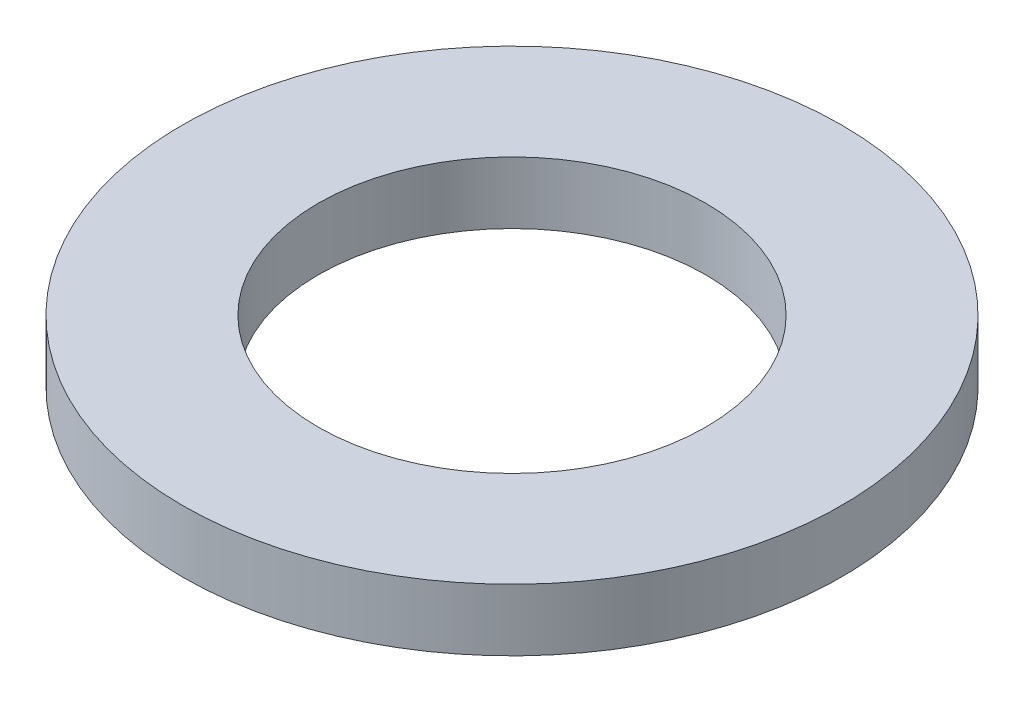
SolidWorks part; units mm, degrees
ref_plane "Front Plane" through (0, 0, 0) normal (0, 0, 1) x (1, 0, 0)
ref_plane "Top Plane" through (0, 0, 0) normal (0, 1, 0) x (1, 0, 0)
ref_plane "Right Plane" through (0, 0, 0) normal (1, 0, 0) x (0, 0, -1)
sketch "Sketch1" plane through (0, 0, 0) normal (0, 1, 0) x (1, 0, 0)
  circle A0 centre (0, 0) radius 42.5
  dimension "FLANGE_OD" = 85
extrude "Boss-Extrude1" add sketch "Sketch1" along normal blind 8
sketch "Sketch2" plane through (0, 0, 0) normal (0, 1, 0) x (1, 0, 0)
  circle A0 centre (0, 0) radius 25
  dimension "BORE_D" = 50
extrude "Cut-Extrude1" cut sketch "Sketch2" along normal through all
sketch "Sketch3" plane through (0, 8, 0) normal (0, 1, 0) x (1, 0, 0)
  circle A0 centre (0, 0) radius 17.6259 construction
  circle A1 centre (-17.6259, 0) radius 3.0571
  dimension "BOLT_D" = 6.1141
  dimension "BOLT_PCD" = 35.2519
extrude "Cut-Extrude2" cut sketch "Sketch3" against normal blind 5.3099 rebuild error yes
pattern_circular "CirPattern1" count 8 over 360 rebuild error yes
